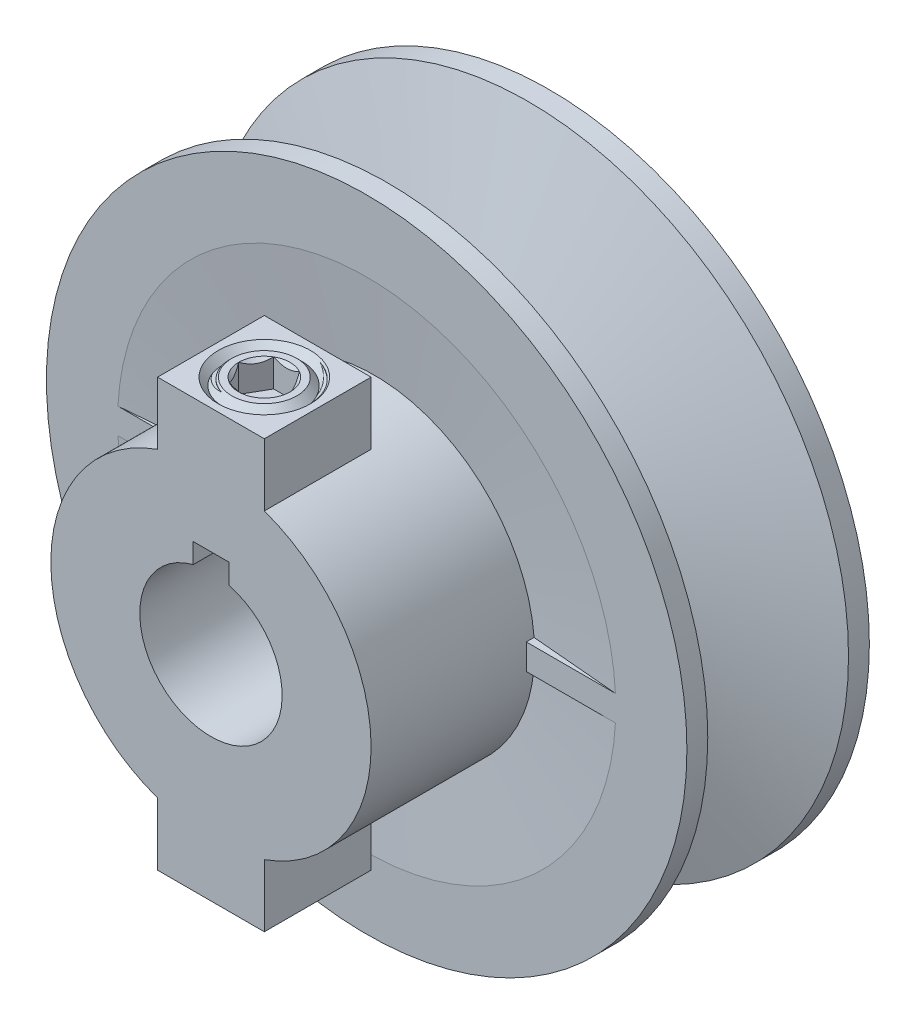
SolidWorks part; units mm, degrees
ref_plane "Front Plane" through (0, 0, 0) normal (0, 0, 1) x (1, 0, 0)
ref_plane "Top Plane" through (0, 0, 0) normal (0, 1, 0) x (1, 0, 0)
ref_plane "Right Plane" through (0, 0, 0) normal (1, 0, 0) x (0, 0, -1)
sketch "Sketch1" plane through (0, 0, 0) normal (1, 0, 0) x (0, 0, -1)
  line L0 (-22.0345, 0) -> (8.1407, 0) construction
  line L1 (-6.2793, 28.575) -> (6.2793, 28.575) construction
  line L2 (6.2793, 28.575) -> (8.1407, 28.575)
  line L5 (-8.1407, 28.575) -> (6.2793, 28.575) construction
  line L7 (-22.0345, 14.2875) -> (-22.0345, -14.2875) construction
  line L10 (-8.1407, 22.225) -> (-7.4463, 14.2875)
  line L13 (-6.2793, 28.575) -> (-2.3965, 15.875)
  line L14 (-2.3965, 15.875) -> (2.3965, 15.875)
  line L15 (2.3965, 15.875) -> (6.2793, 28.575)
  line L16 (8.1407, 6.35) -> (-22.0345, 6.35) construction
  line L17 (0, 28.575) -> (0, 0) construction
  line L18 (-6.2793, 28.575) -> (-8.1407, 28.575)
  line L20 (-22.0345, 0) -> (-22.0345, 6.35) construction
  line L22 (5.3086, 25.4) -> (-5.3086, 25.4) construction
  line L23 (8.1407, 28.575) -> (8.1407, 0) construction
  line L24 (8.1407, 22.225) -> (7.4463, 14.2875)
  line L26 (-22.0345, 14.2875) -> (-7.747, 14.2875)
  line L27 (-7.747, 14.2875) -> (8.1407, 14.2875) construction
  line L28 (-8.1407, 25.4) -> (-5.3086, 25.4) construction
  line L31 (-22.0345, 14.2875) -> (-22.0345, 0)
  line L32 (-8.1407, 22.225) -> (-8.1407, 28.575)
  line L33 (8.1407, 28.575) -> (8.1407, 22.225)
  line L34 (-22.0345, 0) -> (8.1407, 0)
  line L35 (8.1407, 0) -> (8.1407, 14.2875)
  line L37 (-7.4463, 14.2875) -> (7.4463, 14.2875) construction
  line L39 (-7.747, 14.2875) -> (-7.4463, 14.2875)
  line L40 (8.1407, 14.2875) -> (7.4463, 14.2875)
  line L42 (-7.747, 14.2875) -> (-7.747, 0) construction
  point P6 (0, 14.2875)
  point P16 (0, 15.875)
  point P25 (-7.747, 0)
  dimension "D1" = 5
revolve "Revolve1" add sketch "Sketch1" angle 360 about L0
sketch "Sketch2" plane through (0, 0, 0) normal (0, 1, 0) x (0, 0, -1)
  line L0 (-6.2793, 28.575) -> (-8.1407, 28.575) construction
  line L1 (-8.1407, 28.575) -> (-8.1407, -28.575) construction
  line L4 (-7.424, 14.0335) -> (-8.1407, 22.225)
  line L5 (-7.4463, 14.2875) -> (-22.0345, 14.2875) construction
  line L6 (-8.1407, 14.0335) -> (-7.424, 14.0335)
  line L7 (-8.1407, 14.0335) -> (-8.1407, 22.225)
  line L8 (-7.4463, 14.2875) -> (-8.1407, 22.225) construction
  line L11 (8.1407, 14.0335) -> (7.424, 14.0335)
  line L12 (7.424, 14.0335) -> (8.1407, 22.225)
  line L13 (0, 0) -> (0, 28.575) construction
  line L14 (8.1407, 14.0335) -> (8.1407, 22.225)
  dimension "D1" = 0.254
extrude "Boss-Extrude1" add sketch "Sketch2" along normal mid plane 2.286
pattern_circular "CirPattern1" count 2 over 360 of "Boss-Extrude1"
sketch "Sketch3" plane through (0, 0, -8.1407) normal (0, 0, -1) x (-1, 0, 0)
  circle A0 centre (0, 0) radius 6.35
  circle A1 centre (0, 0) radius 25.4 construction
  point P4 (0, 6.35)
extrude "Cut-Extrude1" cut sketch "Sketch3" against normal up to vertex (30.1752 mm away) up to point (0, 0, 22.0345)
sketch "Sketch4" [suppressed] plane through (0, 0, -8.1407) normal (0, 0, -1) x (-1, 0, 0)
  line L0 (2.3812, 9.525) -> (-2.3812, 9.525) construction
  line L1 (2.3813, 11.9062) -> (-2.3813, 11.9062)
  line L2 (2.3813, 11.9062) -> (2.3812, 7.1437)
  line L3 (2.3812, 7.1437) -> (-2.3812, 7.1437)
  line L4 (-2.3813, 11.9062) -> (-2.3812, 7.1437)
  dimension "Keyway Wd." = 3.175
  dimension "Keyway Dp." = 1.5875
extrude "Cut-Extrude2" [suppressed] cut sketch "Sketch4" against normal up to vertex
ref_plane "Plane1" through (0, 14.2875, 0) normal (0, 1, 0) x (-1, 0, 0)
sketch "Sketch5" plane through (0, 14.2875, 0) normal (0, 1, 0) x (-1, 0, 0)
  line L0 (0, 22.0345) -> (0, 0) construction
  line L1 (4.7625, 12.5095) -> (-4.7625, 12.5095)
  line L2 (4.7625, 12.5095) -> (4.7625, 22.0345)
  line L3 (4.7625, 22.0345) -> (-4.7625, 22.0345)
  line L4 (-4.7625, 12.5095) -> (-4.7625, 22.0345)
  line L5 (14.2875, 22.0345) -> (-14.2875, 22.0345) construction
  dimension "D1" = 9.525
extrude "Boss-Extrude2" add sketch "Sketch5" against normal up to surface (5.5796 mm away) from offset 4.7625
mirror "Mirror1" about plane through (0, 0, 0) normal (0, 1, 0) of "Boss-Extrude2"
sketch "Sketch6" plane through (0, 19.05, 0) normal (0, 1, 0) x (-1, 0, 0)
  line L0 (0, 12.5095) -> (0, 22.0345) construction
  line L1 (4.7625, 22.0345) -> (-4.7625, 22.0345) construction
  line L2 (-4.7625, 12.5095) -> (4.7625, 12.5095) construction
  line L7 (0, 21.2407) -> (0, 19.8296) construction
  circle A0 centre (0, 17.272) radius 3.9688 construction
  circle A1 centre (0, 17.272) radius 3.0868
  dimension "D3" = 0.8819
extrude "Cut-Extrude3" cut sketch "Sketch6" against normal up to vertex up to point (0, 0, 22.0345)
sketch "Sketch7" plane through (0, 19.05, 0) normal (0, 1, 0) x (-1, 0, 0)
  circle A0 centre (0, 17.272) radius 3.9688 construction
  circle A1 centre (0, 17.272) radius 3.9688
  point P3 (0, 21.2407)
curve "Helix/Spiral1" pitch 1.4111 height 15.6986 turns 11.125
sketch "Sketch8" plane through (0, 0, 0) normal (1, 0, 0) x (0, 0, -1)
  line L0 (-20.1714, 20.4611) -> (-20.1714, 19.05) construction
  line L1 (-20.1714, 19.05) -> (-21.3935, 19.7556) construction
  line L2 (-21.3935, 19.7556) -> (-20.1714, 20.4611) construction
  line L3 (-20.1714, 19.05) -> (-21.2407, 19.05) construction
  line L4 (-21.2407, 19.05) -> (-21.2407, 19.6674) construction
  line L5 (-21.2407, 19.6674) -> (-21.2407, 19.8438) construction
  line L6 (-20.3242, 19.1382) -> (-20.3242, 20.3729) construction
  line L7 (-21.3935, 19.7556) -> (-21.2407, 19.7556) construction
  line L8 (-20.3242, 19.7556) -> (-20.1714, 19.7556) construction
  line L9 (-20.2478, 20.417) -> (-20.2478, 19.0941)
  line L10 (-20.2478, 19.0941) -> (-21.2407, 19.6674)
  line L11 (-21.2407, 19.6674) -> (-21.2407, 19.8438)
  line L12 (-21.2407, 19.8438) -> (-20.2478, 20.417)
  point P16 (-20.2478, 19.7556)
  dimension "D1" = 1.4111
  dimension "D2" = 0.1764
sweep "Cut-Sweep1" cut profiles "Sketch8" path "Helix/Spiral1"
sketch "Sketch9" plane through (0, 19.05, 0) normal (0, 1, 0) x (-1, 0, 0)
  circle A0 centre (0, 17.272) radius 4.1215
extrude "Cut-Extrude4" cut sketch "Sketch9" against normal through all draft 45
sketch "Sketch10" plane through (0, 0, 0) normal (1, 0, 0) x (0, 0, -1)
  line L0 (-17.272, 19.05) -> (-17.272, 6.35) construction
  line L1 (-21.2407, 7.4193) -> (-21.2407, 17.9807)
  line L2 (-17.272, 19.05) -> (-21.2407, 19.05) construction
  line L3 (-17.272, 19.05) -> (-17.272, 6.35)
  line L4 (-17.272, 6.35) -> (-21.2407, 6.35) construction
  line L5 (-21.2407, 19.05) -> (-21.2407, 6.35) construction
  line L6 (-20.1714, 19.05) -> (-21.2407, 17.9807)
  line L7 (-21.2407, 7.4193) -> (-20.1714, 6.35)
  line L8 (-20.1714, 19.05) -> (-17.272, 19.05)
  line L9 (-20.1714, 6.35) -> (-17.272, 6.35)
  line L10 (-12.5095, 19.05) -> (-22.0345, 19.05) construction
  line L11 (-20.1714, 19.05) -> (-21.2407, 19.05) construction
  line L12 (-21.2407, 19.05) -> (-21.2407, 17.9807) construction
revolve "Revolve3" add sketch "Sketch10" angle 360 about L0
sketch "Sketch11" plane through (0, 19.05, 0) normal (0, 1, 0) x (-1, 0, 0)
  circle A1 centre (0, 17.272) radius 3.9688
  circle A2 centre (0, 17.272) radius 3.9688
  dimension "D1" = 0
curve "Helix/Spiral2" pitch 1.4111 height 14.1111 turns 10
sketch "Sketch12" plane through (0, 0, 0) normal (1, 0, 0) x (0, 0, -1)
  line L0 (-21.3171, 19.7115) -> (-21.3171, 18.3885)
  line L1 (-21.3171, 19.7556) -> (-21.3171, 19.7115) construction
  line L2 (-21.3935, 19.7556) -> (-21.2407, 19.7556) construction
  line L3 (-20.1714, 19.05) -> (-21.3935, 19.7556) construction
  line L4 (-21.3171, 19.7115) -> (-20.3242, 19.1382)
  line L5 (-20.3242, 19.1382) -> (-20.3242, 18.9618)
  line L6 (-20.3242, 18.9618) -> (-21.3171, 18.3885)
  line L7 (-21.3935, 19.7556) -> (-20.1714, 19.05) construction
  line L8 (-20.1714, 19.05) -> (-21.3935, 18.3444) construction
  line L9 (-21.3935, 18.3444) -> (-21.3935, 19.7556) construction
sweep "Cut-Sweep2" cut profiles "Sketch12" path "Helix/Spiral2"
sketch "Sketch13" plane through (0, 19.05, 0) normal (0, 1, 0) x (1, 0, 0)
  line L1 (2.2914, -17.272) -> (1.1457, -15.2876)
  line L2 (1.1457, -15.2876) -> (-1.1457, -15.2876)
  line L3 (-1.1457, -15.2876) -> (-2.2914, -17.272)
  line L4 (-2.2914, -17.272) -> (-1.1457, -19.2564)
  line L5 (-1.1457, -19.2564) -> (1.1457, -19.2564)
  line L6 (1.1457, -19.2564) -> (2.2914, -17.272)
  circle A0 centre (0, -17.272) radius 1.9844 construction
  dimension "D1" = 3.9688
extrude "Cut-Extrude5" cut sketch "Sketch13" against normal blind 2.4805
sketch "Sketch14" plane through (0, 19.05, 0) normal (0, 1, 0) x (1, 0, 0)
  circle A0 centre (0, -17.272) radius 2.2914
extrude "Cut-Extrude6" cut sketch "Sketch14" against normal through all draft 45
sketch "Sketch15" plane through (0, 0, 22.0345) normal (0, 0, 1) x (1, 0, 0)
  line L1 (-1.5875, 4.957) -> (1.5875, 4.957)
  line L2 (-1.5875, 4.957) -> (-1.5875, 7.9375)
  line L3 (-1.5875, 7.9375) -> (1.5875, 7.9375)
  line L4 (1.5875, 4.957) -> (1.5875, 7.9375)
  circle A0 centre (0, 0) radius 6.35 construction
  dimension "D1" = 1.5875
  dimension "D2" = 3.175
extrude "Cut-Extrude7" cut sketch "Sketch15" against normal blind 25.4
equation "\"D3@Sketch6\" = \"Screw Pitch@Sketch6\" * 5 / 8"
equation "\"D4@Helix/Spiral1\" = \"Screw Pitch@Sketch6\""
equation "\"D3@Helix/Spiral1\" = \"D4@Helix/Spiral1\" + ( \"Hub Dia.@Sketch1\" / 2 ) "
equation "\"D1@Sketch8\" = \"D4@Helix/Spiral1\""
equation "\"D2@Sketch8\" = \"D1@Sketch8\" / 8"
equation "\"D4@Helix/Spiral2\" = \"D4@Helix/Spiral1\""
equation "\"D3@Helix/Spiral2\" = \"D4@Helix/Spiral2\" + \"Screw Length@Sketch10\""
equation "\"D1@Sketch13\" = \"Screw OD@Sketch6\" / 2"
equation "\"D1@Cut-Extrude5\" = \"D1@Sketch13\" * 5 / 8"
